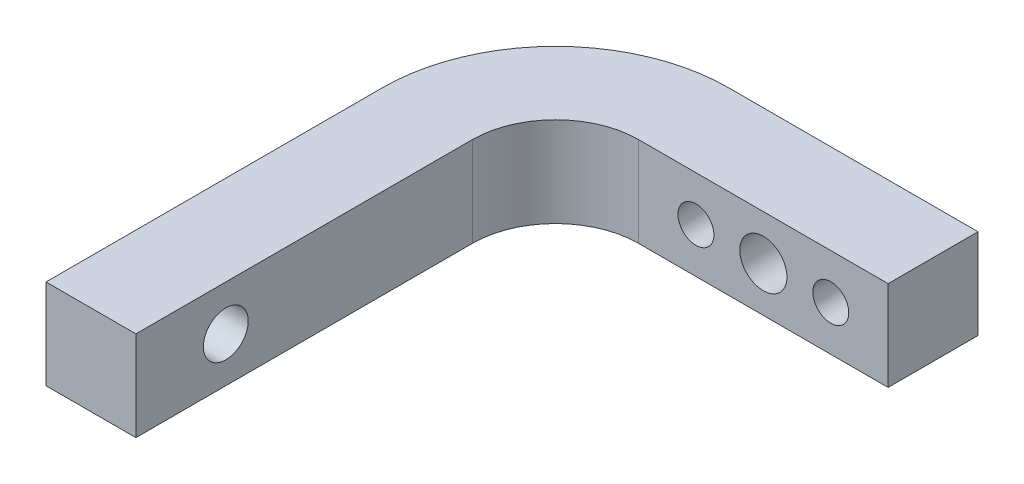
SolidWorks part; units mm, degrees
ref_plane "Front Plane" through (0, 0, 0) normal (0, 0, 1) x (1, 0, 0)
ref_plane "Top Plane" through (0, 0, 0) normal (0, 1, 0) x (1, 0, 0)
ref_plane "Right Plane" through (0, 0, 0) normal (1, 0, 0) x (0, 0, -1)
ref_axis "Z" through (0, 0, -2.267) along (0, 0, 1)
sketch "Sketch1" plane through (0, 0, 0) normal (0, 1, 0) x (1, 0, 0)
  line L0 (-11.1, 0) -> (11.1, 0)
  line L1 (-26.5, -15.4) -> (-26.5, -45.34)
  line L2 (-26.5, -45.34) -> (-18.5, -45.34)
  line L3 (-18.5, -45.34) -> (-18.5, -15.4)
  line L4 (-11.1, -8) -> (11.1, -8)
  line L5 (0, -8) -> (0, 0) construction
  line L6 (18.5, -45.34) -> (18.5, -15.4) construction
  line L7 (26.5, -45.34) -> (18.5, -45.34) construction
  line L8 (26.5, -15.4) -> (26.5, -45.34) construction
  line L9 (11.1, 0) -> (11.1, -8)
  arc A0 (-11.1, 0) -> (-26.5, -15.4) centre (-11.1, -15.4) ccw
  arc A1 (-18.5, -15.4) -> (-11.1, -8) centre (-11.1, -15.4) cw
  arc A2 (18.5, -15.4) -> (11.1, -8) centre (11.1, -15.4) ccw construction
  arc A3 (11.1, 0) -> (26.5, -15.4) centre (11.1, -15.4) cw construction
  dimension "D3" = 7.4
  dimension "D1" = 37
  dimension "D2" = 8
  dimension "D4" = 37.34
extrude "Boss-Extrude1" add sketch "Sketch1" along normal blind 4 and the other way blind 4
sketch "Sketch2" plane through (-18.5, 0, 0) normal (-1, 0, 0) x (0, 0, 1)
  line L1 (20.68, 0) -> (-20.68, 0) construction
  line L2 (0, -4.4) -> (0, 4.4) construction
  circle A0 centre (37.34, 0) radius 2
  dimension "D1" = 4
  dimension "D2" = 37.34
extrude "Cut-Extrude1" cut sketch "Sketch2" against normal through all both and the other way through all
ref_axis "Axis2" through (-60.1767, 0, 37.34) along (1, 0, 0)
sketch "Sketch3" plane through (0, 0, 0) normal (0, 0, -1) x (-1, 0, 0)
  line L0 (-6, 0) -> (6, 0) construction
  circle A0 centre (0, 0) radius 2.1
  circle A1 centre (-6, 0) radius 1.6
  circle A2 centre (6, 0) radius 1.6
  dimension "D1" = 4.2
  dimension "D3" = 3.2
  dimension "D2" = 12
extrude "Cut-Extrude2" cut sketch "Sketch3" against normal through all
equation "\"width\"= \"EyeDiameter\" + \"EyeClearance\""
equation "\"prongwidth\"= 8"
equation "\"D2@Sketch1\"=\"prongwidth\""
equation "\"D3@Sketch1\"=\"width\"/5"
equation "\"pronglength\"= \"BasePlaneDistance\"'model implicitly adds clearance (of prongwidth) to the hole drilled at the baseplanedistance"
equation "\"D4@Sketch1\"=\"pronglength\""
equation "\"D1@Boss-Extrude1\"=\"prongwidth\"/2"
equation "\"D2@Boss-Extrude1\"=\"prongwidth\"/2"
equation "\"lbracket-plane-to-axis\"= \"BasePlaneDistance\""
equation "\"D2@Sketch2\"=\"lbracket-plane-to-axis\""
equation "\"EyeDiameter\" = 35"
equation "\"BasePlaneDistance\" = \"EyeDiameter\"/2+19.84"
equation "\"EyeClearance\" = 2"
equation "\"D1@Sketch1\"=\"EyeDiameter\"+\"EyeClearance\""
